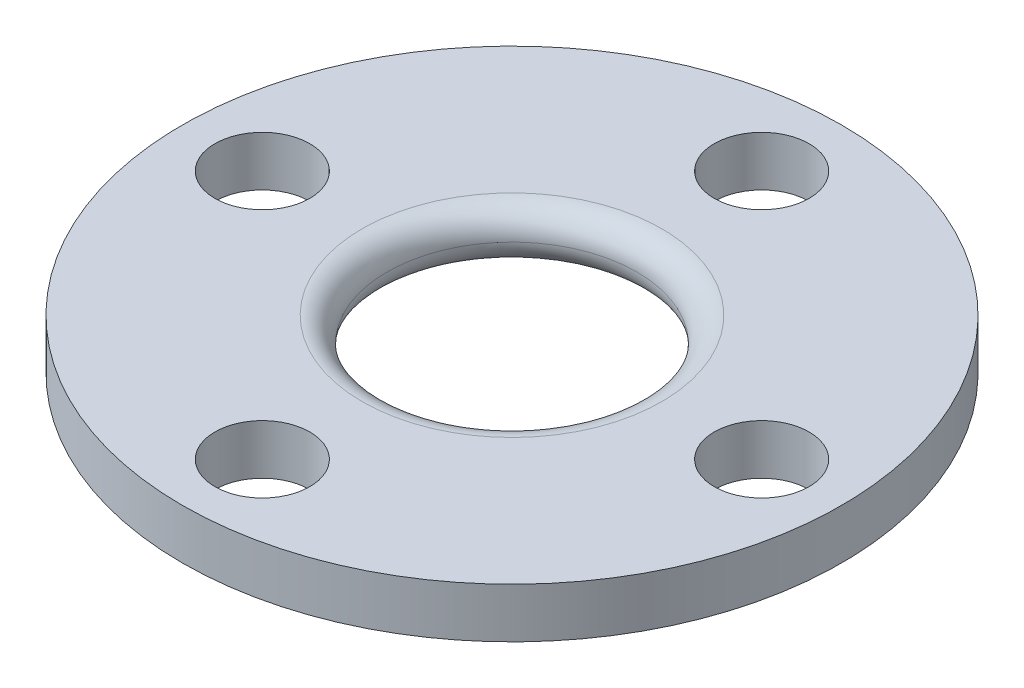
SolidWorks part; units mm, degrees
ref_plane "Front Plane" through (0, 0, 0) normal (0, 0, 1) x (1, 0, 0)
ref_plane "Top Plane" through (0, 0, 0) normal (0, 1, 0) x (1, 0, 0)
ref_plane "Right Plane" through (0, 0, 0) normal (1, 0, 0) x (0, 0, -1)
sketch "Sketch2" plane through (0, 0, 0) normal (0, 1, 0) x (1, 0, 0)
  circle A0 centre (0, 0) radius 13.2
extrude "Boss-Extrude1" add sketch "Sketch2" along normal blind 2
sketch "Sketch3" plane through (0, 2, 0) normal (0, 1, 0) x (1, 0, 0)
  line L0 (0, 0) -> (0, 10) construction
  circle A0 centre (0, 10) radius 1.9
  dimension "D2" = 3.8
  dimension "D1" = 10
extrude "Cut-Extrude1" cut sketch "Sketch3" against normal blind 2
sketch "Sketch4" plane through (0, 2, 0) normal (0, 1, 0) x (1, 0, 0)
  circle A0 centre (0, 0) radius 5
extrude "Cut-Extrude2" cut sketch "Sketch4" against normal blind 2
pattern_circular "CirPattern1" count 4 every 90 about axis through (0, 0, 0) along (0, 1, 0) of "Cut-Extrude1"
sketch "Sketch5" plane through (0, 2, 0) normal (0, 1, 0) x (1, 0, 0)
  line L0 (0, 11.9) -> (0, 13.2) construction
  circle A0 centre (0, 10) radius 1.9 construction
  circle A1 centre (0, 0) radius 13.2 construction
  dimension "D1" = 1.3
fillet "Fillet2" radius 1 2 edges at (0, 0, 5) (0, 2, 5)
